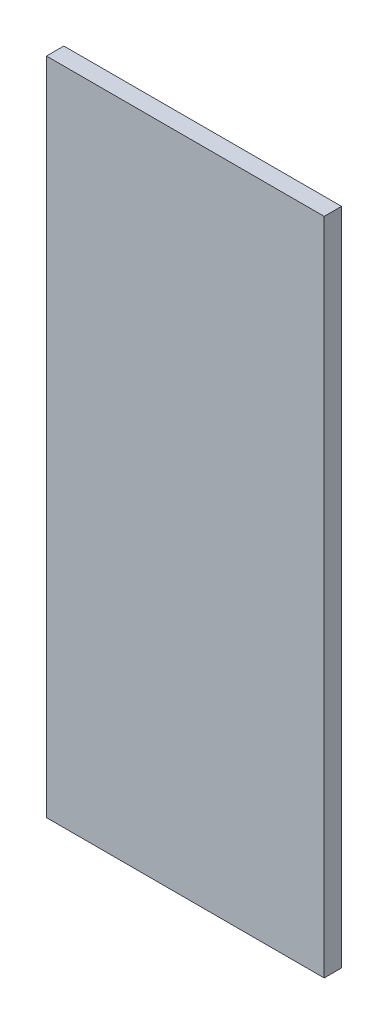
SolidWorks part; units mm, degrees
material "Бальса"
ref_plane "Спереди" through (0, 0, 0) normal (0, 0, 1) x (1, 0, 0)
ref_plane "Сверху" through (0, 0, 0) normal (0, 1, 0) x (1, 0, 0)
ref_plane "Справа" through (0, 0, 0) normal (1, 0, 0) x (0, 0, -1)
sketch "Эскиз2" plane through (0, 0, 0) normal (0, 0, 1) x (1, 0, 0)
  line L1 (0, 0) -> (160, 0)
  line L2 (0, 0) -> (0, 380)
  line L3 (0, 380) -> (160, 380)
  line L4 (160, 0) -> (160, 380)
  dimension "D1" = 160
  dimension "D2" = 380
extrude "Бобышка-Вытянуть1" add sketch "Эскиз2" along normal blind 10
sketch "Эскиз3" [suppressed] plane through (0, 0, 0) normal (-1, 0, 0) x (0, 0, 1)
  line L0 (10, 330) -> (0, 320)
  line L1 (0, 330) -> (0, 0) construction
  line L2 (0, 320) -> (0, 330)
  line L3 (0, 330) -> (10, 330)
  dimension "D1" = 45
sketch "Эскиз4" [suppressed] plane through (0, 0, 0) normal (-1, 0, 0) x (0, 0, 1)
  line L0 (0, 0) -> (10, 10)
  line L1 (10, 50) -> (10, 0) construction
  line L2 (10, 10) -> (10, 0)
  line L3 (10, 0) -> (0, 0)
  dimension "D1" = 45
sketch "Эскиз5" [suppressed] plane through (0, 0, 0) normal (0, -1, 0) x (-1, 0, 0)
  line L0 (-560, -10) -> (-550, 0)
  line L1 (0, 0) -> (-560, 0) construction
  line L2 (-550, 0) -> (-560, 0)
  line L3 (-560, 0) -> (-560, -10)
  dimension "D1" = 45
